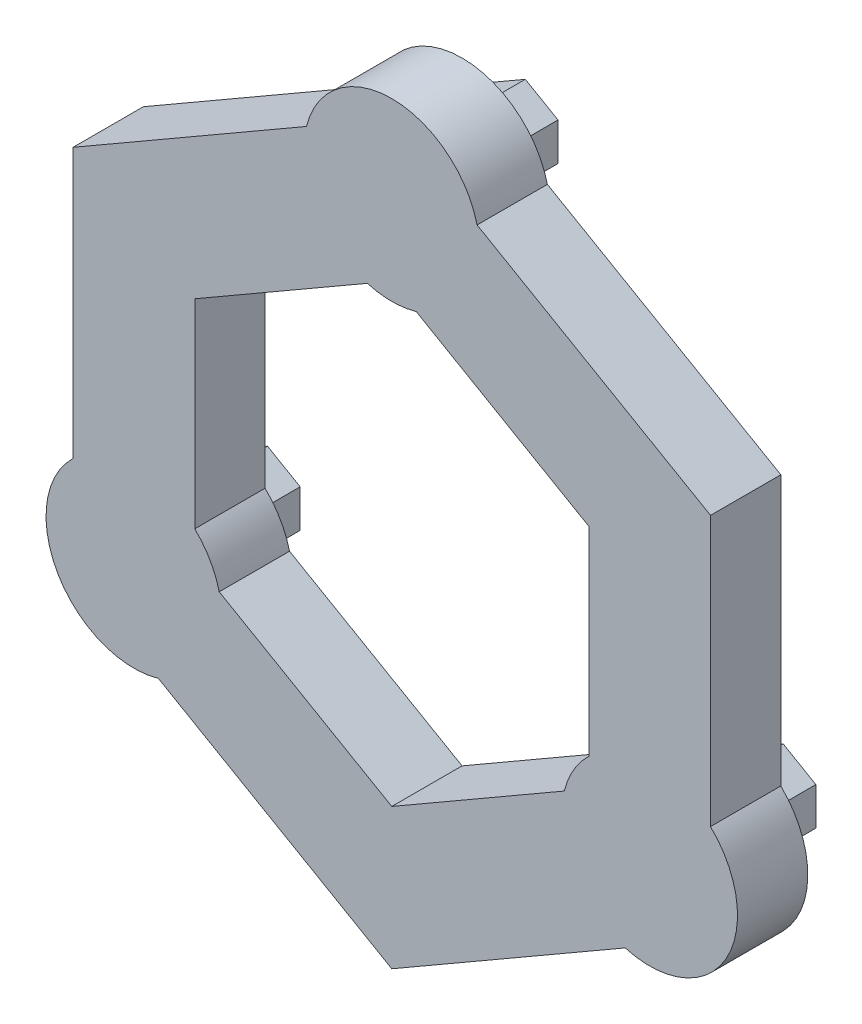
SolidWorks part; units mm, degrees
ref_plane "Front Plane" through (0, 0, 0) normal (0, 0, 1) x (1, 0, 0)
ref_plane "Top Plane" through (0, 0, 0) normal (0, 1, 0) x (1, 0, 0)
ref_plane "Right Plane" through (0, 0, 0) normal (1, 0, 0) x (0, 0, -1)
sketch "Sketch1" plane through (0, 0, 0) normal (0, 0, 1) x (1, 0, 0)
  line L0 (0, 21.1785) -> (0, 0) construction
  line L1 (0, 0) -> (18.3411, -10.5892) construction
  line L2 (0, 0) -> (-18.3411, -10.5892) construction
  line L3 (0, 21.1785) -> (0, 42.357) construction
  line L4 (0, -10.45) -> (0, 10.45) construction
  line L5 (18.3411, -10.5892) -> (36.6822, -21.1785) construction
  line L6 (-18.3411, -10.5892) -> (-36.6822, -21.1785) construction
  circle A0 centre (0, 0) radius 21.1785 construction
  circle A1 centre (0, 42.357) radius 21.1785 construction
  circle A2 centre (36.6822, -21.1785) radius 21.1785 construction
  circle A3 centre (-36.6822, -21.1785) radius 21.1785 construction
  dimension "D3" = 42.357
  dimension "D4" = 42.357
  dimension "D1" = 120
  dimension "D2" = 120
sketch "Sketch3" plane through (0, 0, 0) normal (0, 0, 1) x (1, 0, 0)
  line L0 (0, -10.45) -> (0, 10.45) construction
  line L1 (0, 42.357) -> (-36.6822, 21.1785) construction
  line L2 (-36.6822, 21.1785) -> (-36.6822, -21.1785) construction
  line L3 (-36.6822, -21.1785) -> (0, -42.357) construction
  line L4 (0, -42.357) -> (36.6822, -21.1785) construction
  line L5 (36.6822, -21.1785) -> (36.6822, 21.1785) construction
  line L6 (36.6822, 21.1785) -> (0, 42.357) construction
  line L7 (0, 32.357) -> (-28.022, 16.1785)
  line L8 (-28.022, 16.1785) -> (-28.022, -16.1785)
  line L9 (-28.022, -16.1785) -> (0, -32.357)
  line L10 (0, -32.357) -> (28.022, -16.1785)
  line L11 (28.022, -16.1785) -> (28.022, 16.1785)
  line L12 (28.022, 16.1785) -> (0, 32.357)
  line L13 (0, 52.357) -> (-45.3425, 26.1785)
  line L14 (-45.3425, 26.1785) -> (-45.3425, -26.1785)
  line L15 (-45.3425, -26.1785) -> (0, -52.357)
  line L16 (0, -52.357) -> (45.3425, -26.1785)
  line L17 (45.3425, -26.1785) -> (45.3425, 26.1785)
  line L18 (45.3425, 26.1785) -> (0, 52.357)
  line L19 (0, 21.1785) -> (0, 42.357) construction
  line L20 (-45.3425, 26.1785) -> (-28.022, 16.1785) construction
  circle A0 centre (0, 0) radius 36.6822 construction
  circle A1 centre (0, 0) radius 28.022 construction
  circle A2 centre (0, 0) radius 45.3425 construction
  circle A3 centre (-36.6822, -21.1785) radius 12.5
  circle A4 centre (36.6822, -21.1785) radius 12.5
  circle A5 centre (0, 42.357) radius 12.5
  point P35 (-36.6822, 21.1785)
  dimension "D2" = 25
  dimension "D1" = 20
extrude "Boss-Extrude2" add sketch "Sketch3" along normal mid plane 10 contours A5 L7 L8 A3 L9 L10 A4 L11 L12 | L14 A3 L15 | L16 A4 L17 | L18 A5 L13 | L14 L15 L16 L17 L18 L13 region at (0, 0, 0) region at (0, 54.5963, 0) region at (-45.6105, -19.1716, 0) region at (47.9358, -16.3847, 0)
sketch "Sketch4" plane through (0, 0, -5) normal (0, 0, -1) x (-1, 0, 0)
  line L1 (-41.3322, -23.8632) -> (-36.6822, -26.5479)
  line L2 (-36.6822, -26.5479) -> (-32.0322, -23.8632)
  line L3 (-32.0322, -23.8632) -> (-32.0322, -18.4938)
  line L4 (-32.0322, -18.4938) -> (-36.6822, -15.8091)
  line L5 (-36.6822, -15.8091) -> (-41.3322, -18.4938)
  line L6 (-41.3322, -18.4938) -> (-41.3322, -23.8632)
  line L7 (41.3322, -23.8632) -> (41.3322, -18.4938)
  line L8 (41.3322, -18.4938) -> (36.6822, -15.8091)
  line L9 (36.6822, -15.8091) -> (32.0322, -18.4938)
  line L10 (32.0322, -18.4938) -> (32.0322, -23.8632)
  line L11 (32.0322, -23.8632) -> (36.6822, -26.5479)
  line L12 (36.6822, -26.5479) -> (41.3322, -23.8632)
  line L13 (0, 47.7264) -> (-4.65, 45.0417)
  line L14 (-4.65, 45.0417) -> (-4.65, 39.6723)
  line L15 (-4.65, 39.6723) -> (0, 36.9876)
  line L16 (0, 36.9876) -> (4.65, 39.6723)
  line L17 (4.65, 39.6723) -> (4.65, 45.0417)
  line L18 (4.65, 45.0417) -> (0, 47.7264)
  circle A0 centre (-36.6822, -21.1785) radius 4.65 construction
  circle A1 centre (36.6822, -21.1785) radius 4.65 construction
  circle A2 centre (0, 42.357) radius 4.65 construction
  dimension "D1" = 9.3
extrude "Boss-Extrude3" add sketch "Sketch4" along normal blind 9
equation "\"sN\"= 12'Sun teeth"
equation "\"rN\"= 36'Ring teeth"
equation "\"pN\"= ( \"rN\" - \"sN\" ) / 2'Planet teeth"
equation "\"m\"= 3.5'Modulus"
equation "\"sRD\"= \"sN\" * \"m\"'Sun root diam"
equation "\"rRD\"= \"rN\" * \"m\"'Ring root diam"
equation "\"pRD\"= \"pN\" * \"m\"'Planet root diam"
equation "\"D3@Sketch1\"=\"sRD\"*\"sF\""
equation "\"D4@Sketch1\"=\"pRD\"*\"sF\""
equation "\"sF\"= 1.0085'Scale factor"
